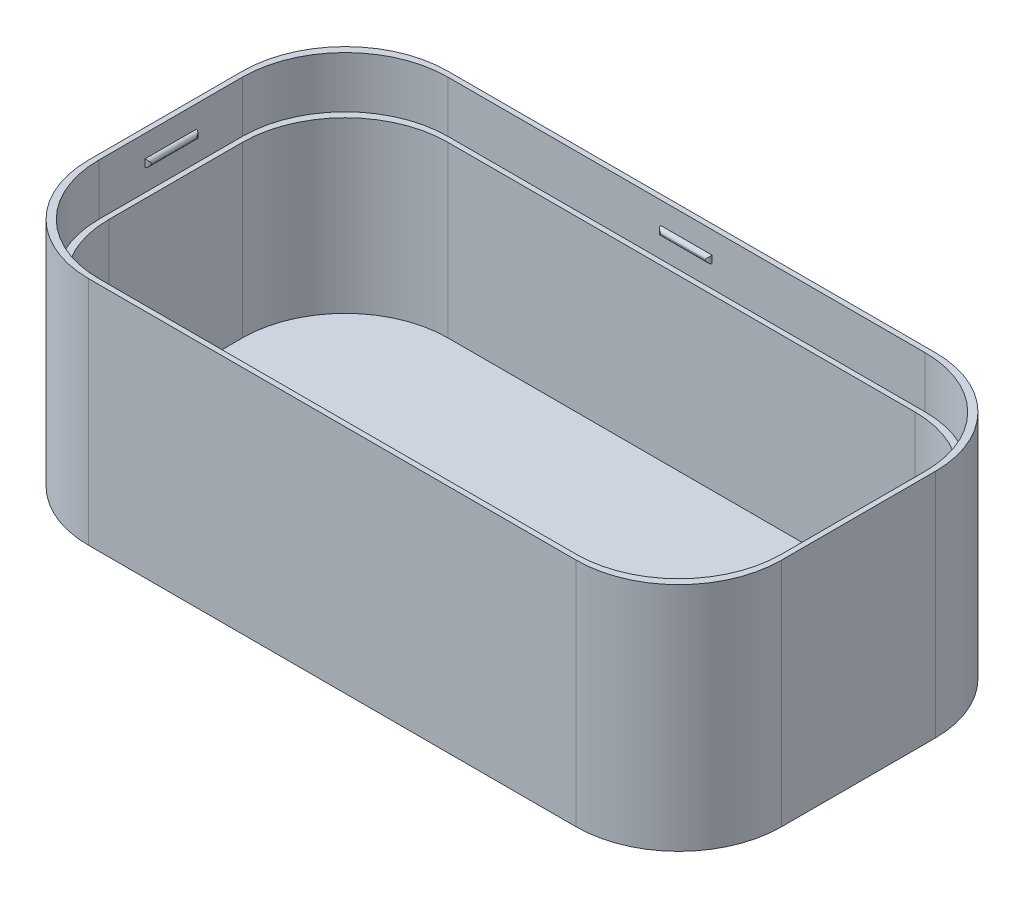
SolidWorks part; units mm, degrees
ref_plane "前视基准面" through (0, 0, 0) normal (0, 0, 1) x (1, 0, 0)
ref_plane "上视基准面" through (0, 0, 0) normal (0, 1, 0) x (1, 0, 0)
ref_plane "右视基准面" through (0, 0, 0) normal (1, 0, 0) x (0, 0, -1)
other "Configuration Table"
sketch "草图1" plane through (0, 0, 0) normal (0, 1, 0) x (1, 0, 0)
  line L1 (-67.5, -35) -> (67.5, -35)
  line L2 (-67.5, -35) -> (-67.5, 35)
  line L3 (-67.5, 35) -> (67.5, 35)
  line L4 (67.5, -35) -> (67.5, 35)
  line L5 (-67.5, -35) -> (67.5, 35) construction
  line L6 (-67.5, 35) -> (67.5, -35) construction
  point P0 (0, 0)
  dimension "D1" = 135
  dimension "D2" = 70
extrude "凸台-拉伸1" add sketch "草图1" along normal blind 45 contours L1 L4 L3 L2
sketch "草图2" plane through (0, 45, 0) normal (0, 1, 0) x (1, 0, 0)
  line L16 (-66.5, 34) -> (-66.5, -34)
  line L17 (-66.5, -34) -> (66.5, -34)
  line L18 (66.5, -34) -> (66.5, 34)
  line L19 (66.5, 34) -> (-66.5, 34)
  line L20 (-66.5, 34) -> (-66.5, -34)
  line L21 (-66.5, -34) -> (66.5, -34)
  line L22 (66.5, -34) -> (66.5, 34)
  line L23 (66.5, 34) -> (-66.5, 34)
  dimension "D1" = 1
extrude "切除-拉伸1" cut sketch "草图2" against normal blind 10
sketch "草图4" plane through (0, 35, 0) normal (0, 1, 0) x (1, 0, 0)
  line L4 (-65.5, 33) -> (-65.5, -33)
  line L5 (-65.5, 33) -> (-65.5, -33)
  line L6 (-65.5, -33) -> (65.5, -33)
  line L7 (-65.5, -33) -> (65.5, -33)
  line L8 (65.5, 33) -> (-65.5, 33)
  line L9 (65.5, -33) -> (65.5, 33)
  line L10 (65.5, -33) -> (65.5, 33)
  line L12 (65.5, 33) -> (-65.5, 33)
  dimension "D1" = 1
extrude "切除-拉伸3" cut sketch "草图4" against normal offset from surface (33 mm away) 2 up to face at (0, 0, 0)
fillet "圆角3" radius 20 12 edges at (67.5, 22.5, -35) (-67.5, 22.5, -35) (-67.5, 22.5, 35) (67.5, 22.5, 35) (66.5, 40, -34) (-66.5, 40, -34) (-66.5, 40, 34) (66.5, 40, 34) (65.5, 18.5, 33) (-65.5, 18.5, 33) (65.5, 18.5, -33) (-65.5, 18.5, -33) tangent propagation no
sketch "草图5" plane through (0, 0, -34) normal (0, 0, 1) x (1, 0, 0)
  line L0 (0, 45) -> (0, 35) construction
  line L2 (-5, 39.3) -> (5, 39.3)
  line L3 (-5, 39.3) -> (-5, 40.7)
  line L4 (-46.5, 35) -> (46.5, 35)
  line L5 (46.5, 35) -> (46.5, 45)
  line L6 (46.5, 45) -> (-46.5, 45)
  line L7 (46.5, 35) -> (46.5, 45) construction
  line L8 (-46.5, 35) -> (46.5, 35) construction
  line L10 (46.5, 45) -> (-46.5, 45) construction
  line L12 (-5, 40.7) -> (5, 40.7)
  line L13 (5, 39.3) -> (5, 40.7)
  line L14 (-5, 39.3) -> (5, 40.7) construction
  line L15 (-5, 40.7) -> (5, 39.3) construction
  line L19 (-46.5, 45) -> (-46.5, 35)
  line L20 (-46.5, 45) -> (-46.5, 35) construction
  point P6 (0, 40)
  dimension "D2" = 10
  dimension "D3" = 1.4
  dimension "D1" = 0
extrude "凸台-拉伸2" add sketch "草图5" along normal blind 0.7
fillet "圆角5" radius 0.7 4 edges at (5, 40, -33.3) (-5, 40, -33.3) (0, 39.3, -33.3) (0, 40.7, -33.3)
mirror "镜向2" about plane through (0, 0, 0) normal (0, 0, 1) of "圆角5", "凸台-拉伸2"
sketch "草图6" plane through (-66.5, 0, 0) normal (1, 0, 0) x (0, 0, -1)
  line L0 (0, 45) -> (0, 35) construction
  line L1 (14, 35) -> (-14, 35) construction
  line L2 (-5, 39.3) -> (5, 39.3)
  line L3 (-5, 39.3) -> (-5, 40.7)
  line L4 (14, 35) -> (14, 45) construction
  line L5 (14, 45) -> (-14, 45) construction
  line L6 (14, 35) -> (14, 45) construction
  line L7 (14, 45) -> (-14, 45) construction
  line L12 (-5, 40.7) -> (5, 40.7)
  line L13 (5, 39.3) -> (5, 40.7)
  line L14 (-5, 39.3) -> (5, 40.7) construction
  line L15 (-5, 40.7) -> (5, 39.3) construction
  line L16 (14, 35) -> (-14, 35) construction
  line L17 (-14, 45) -> (-14, 35) construction
  line L18 (-14, 45) -> (-14, 35) construction
  point P7 (0, 40)
  dimension "D2" = 10
  dimension "D3" = 1.4
extrude "凸台-拉伸3" add sketch "草图6" along normal blind 0.7
fillet "圆角6" radius 0.7 4 edges at (-65.8, 40, -5) (-65.8, 40, 5) (-65.8, 39.3, 0) (-65.8, 40.7, 0)
mirror "镜向3" about plane through (0, 0, 0) normal (1, 0, 0) of "圆角6", "凸台-拉伸3"
